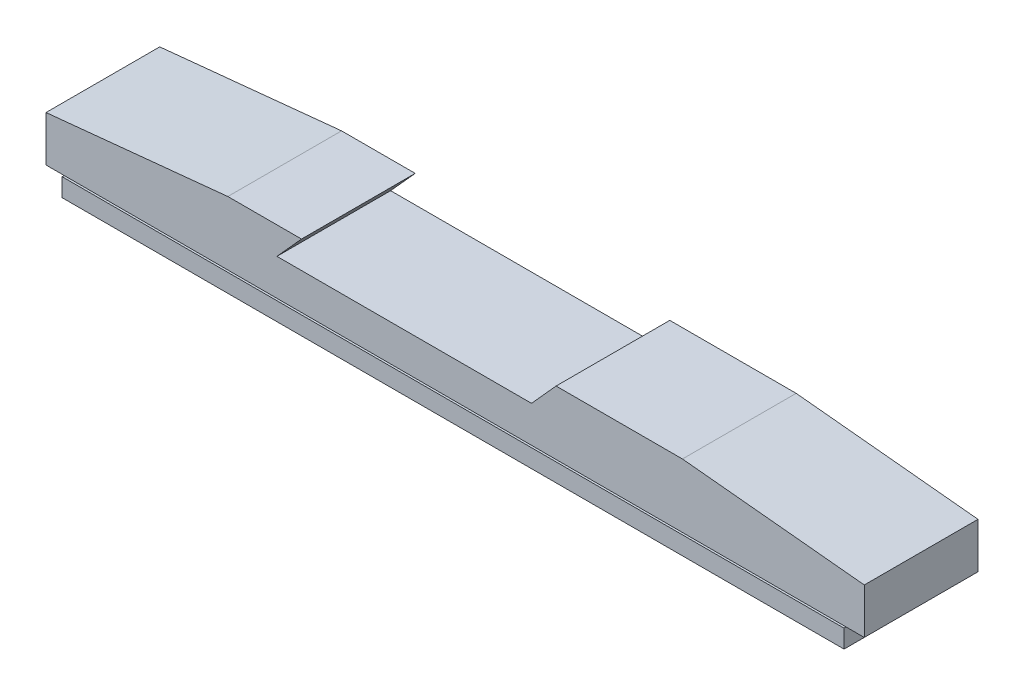
SolidWorks part; units mm, degrees
ref_plane "Front Plane" through (0, 0, 0) normal (0, 0, 1) x (1, 0, 0)
ref_plane "Top Plane" through (0, 0, 0) normal (0, 1, 0) x (1, 0, 0)
ref_plane "Right Plane" through (0, 0, 0) normal (1, 0, 0) x (0, 0, -1)
sketch "Sketch1" plane through (0, 0, 0) normal (1, 0, 0) x (0, 0, -1)
  line L0 (0, 10.7333) -> (0, -56) construction
  line L1 (-31.2667, 35) -> (31.2667, 35)
  line L2 (-31.2667, 35) -> (-31.2667, 0)
  line L3 (-31.2667, 0) -> (31.2667, 0)
  line L4 (31.2667, 35) -> (31.2667, 0)
  line L5 (-11.6667, 0) -> (11.6667, 0)
  line L6 (-11.6667, 0) -> (-11.6667, -10)
  line L8 (11.6667, 0) -> (11.6667, -10)
  line L9 (-22.4, -10) -> (-11.6667, -10)
  line L10 (-22.4, -10) -> (-22.4, -20)
  line L11 (-22.4, -20) -> (22.4, -20)
  line L12 (22.4, -10) -> (22.4, -20)
  line L13 (11.6667, -10) -> (22.4, -10)
  dimension "D1" = 35
  dimension "D2" = 10
  dimension "D3" = 10
extrude "Boss-Extrude1" add sketch "Sketch1" along normal blind 430 contours L5 L0 L11 L12 L13 L8 | L0 L3 L6 L9 L10 L11 region at (0, -11.5753, -9.3621) region at (0, -11.5753, 9.3621)
extrude "Boss-Extrude2" add sketch "Sketch1<3>" along normal blind 450 contours L4 L1 L2 L3 L5 region at (0, 17.5, 0)
sketch "Sketch1<3>" plane through (0, 0, 0) normal (1, 0, 0) x (0, 0, -1) same geometry as "Sketch1"
sketch "Sketch2" plane through (0, 0, 31.2667) normal (0, 0, 1) x (1, 0, 0)
  line L0 (0, 25) -> (100, 35)
  line L1 (0, 35) -> (0, 0) construction
  line L2 (450, 35) -> (0, 35) construction
  line L3 (100, 35) -> (140.5061, 35)
  line L4 (140.5061, 35) -> (127, 20)
  line L5 (127, 20) -> (267, 20)
  line L6 (267, 20) -> (280.5061, 35)
  line L7 (280.5061, 35) -> (350, 35)
  line L8 (350, 35) -> (450, 25)
  line L9 (450, 35) -> (450, 0) construction
  line L10 (450, 0) -> (0, 0) construction
  line L11 (0, 25) -> (0, 35)
  line L12 (0, 35) -> (450, 35)
  line L13 (450, 35) -> (450, 25)
  line M4 (0, 35) -> (0, 0)
  line M6 (450, 0) -> (450, 35)
  line M7 (450, 35) -> (0, 35)
  dimension "D1" = 48
  dimension "D2" = 140
  dimension "D3" = 100
  dimension "D4" = 100
  dimension "D5" = 25
  dimension "D6" = 127
  dimension "D7" = 20
extrude "Cut-Extrude1" cut sketch "Sketch2" against normal up to next contours L5 L6 L4 M7 | L0 M4 M7 | L8 M7 M6 | L12 L13 L8 L7 L6 L5 L4 L3 L0 L11 region at (33.3333, 31.6667, 31.2667) region at (416.6667, 31.6667, 31.2667) region at (203.753, 27.5, 31.2667)
